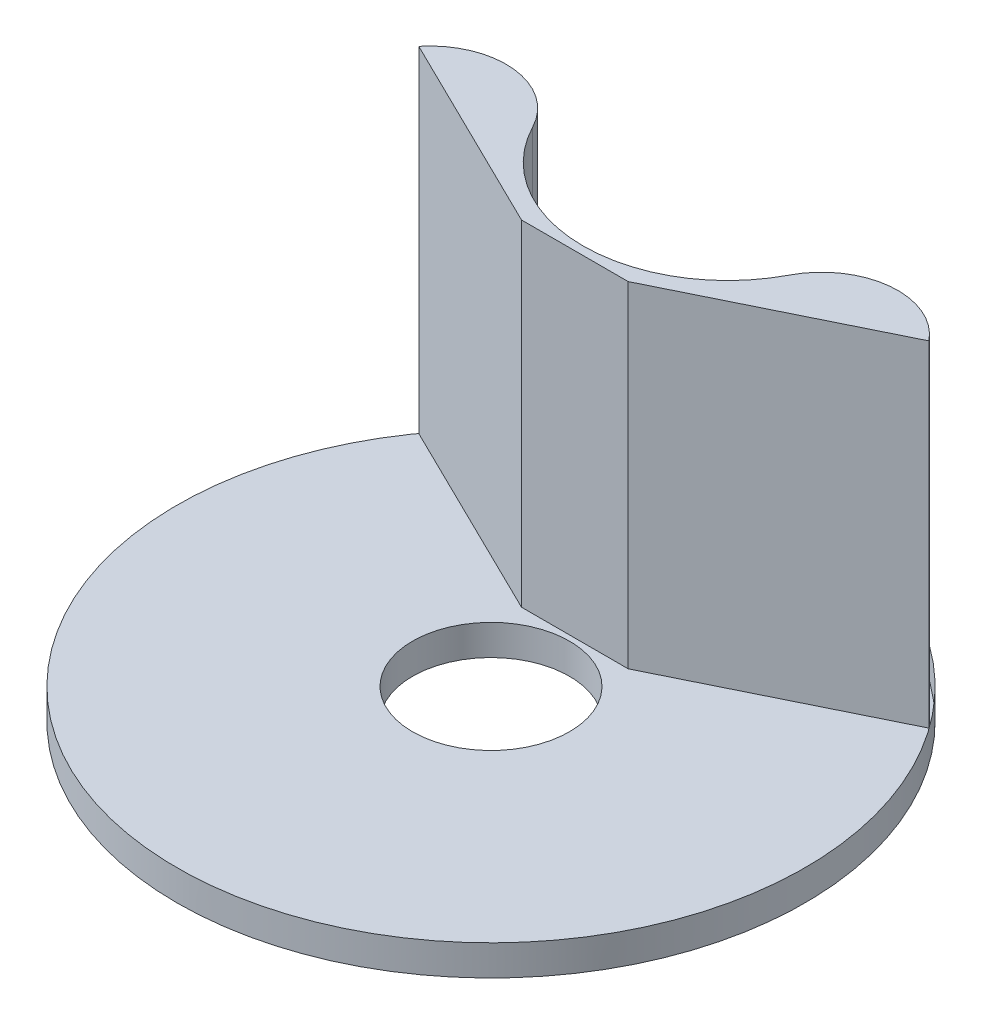
SolidWorks part; units mm, degrees
ref_plane "Front Plane" through (0, 0, 0) normal (0, 0, 1) x (1, 0, 0)
ref_plane "Top Plane" through (0, 0, 0) normal (0, 1, 0) x (1, 0, 0)
ref_plane "Right Plane" through (0, 0, 0) normal (1, 0, 0) x (0, 0, -1)
sketch "Sketch1" plane through (0, 0, 0) normal (0, 1, 0) x (1, 0, 0)
  circle A0 centre (0, 0) radius 20.6
  dimension "D1" = 41.2
extrude "Boss-Extrude1" add sketch "Sketch1" along normal blind 2
sketch "Sketch2" plane through (0, 2, 0) normal (0, 1, 0) x (1, 0, 0)
  circle A0 centre (0, 0) radius 5.15
  dimension "D1" = 10.3
extrude "Cut-Extrude1" cut sketch "Sketch2" against normal blind 3
sketch "Sketch3" plane through (0, 2, 0) normal (0, 1, 0) x (1, 0, 0)
  circle A0 centre (0, 13) radius 6.5
  dimension "D2" = 13
  dimension "D1" = 13
extrude "Cut-Extrude2" cut sketch "Sketch3" against normal blind 2
sketch "Sketch4" plane through (0, 2, 0) normal (0, 1, 0) x (1, 0, 0)
  line L0 (-3.5, 5.5) -> (-16.744, 12)
  line L1 (3.5, 5.5) -> (16.744, 12)
  line L4 (-3.5, 5.5) -> (3.5, 5.5)
  arc A0 (-16.744, 12) -> (-9, 18.53) centre (0, 0) cw
  circle A1 centre (0, 0) radius 20.6 construction
  arc A4 (9, 18.53) -> (16.744, 12) centre (0, 0) cw
  arc A6 (-9, 18.53) -> (9, 18.53) centre (0, 15.5297) ccw
  dimension "D1" = 12
  dimension "D2" = 12
  dimension "D3" = 5.5
  dimension "D4" = 5.5
  dimension "D5" = 3.5
  dimension "D6" = 3.5
  dimension "D7" = 9
  dimension "D8" = 9
extrude "Boss-Extrude4" add sketch "Sketch4" along normal blind 22
fillet "Fillet1" radius 5 2 edges at (-9, 13, -18.53) (9, 13, -18.53)
